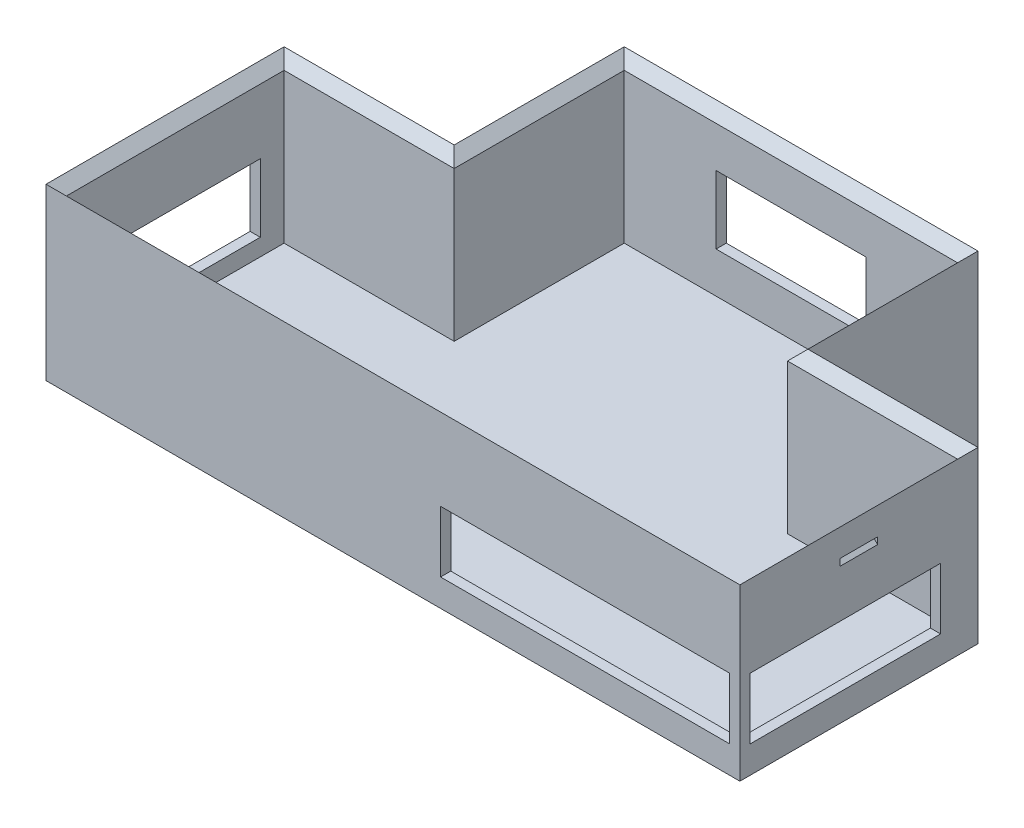
SolidWorks part; units mm, degrees
ref_plane "Front Plane" through (0, 0, 0) normal (0, 0, 1) x (1, 0, 0)
ref_plane "Top Plane" through (0, 0, 0) normal (0, 1, 0) x (1, 0, 0)
ref_plane "Right Plane" through (0, 0, 0) normal (1, 0, 0) x (0, 0, -1)
sketch "Sketch1" plane through (0, 0, 0) normal (0, 1, 0) x (1, 0, 0)
  line L12 (-88.7649, 6.3436) -> (115.2351, 6.3436)
  line L13 (115.2351, 6.3436) -> (115.2351, 76.3436)
  line L14 (115.2351, 76.3436) -> (65.2351, 76.3436)
  line L15 (65.2351, 76.3436) -> (65.2351, 126.3436)
  line L16 (65.2351, 126.3436) -> (-38.7649, 126.3436)
  line L17 (-38.7649, 126.3436) -> (-38.7649, 76.3436)
  line L18 (-38.7649, 76.3436) -> (-88.7649, 76.3436)
  line L19 (-88.7649, 76.3436) -> (-88.7649, 6.3436)
  dimension "D1" = 104
  dimension "D2" = 50
  dimension "D3" = 50
  dimension "D4" = 50
  dimension "D5" = 50
  dimension "D6" = 70
extrude "Boss-Extrude1" add sketch "Sketch1" along normal blind 50
sketch "Sketch4" plane through (0, 50, 0) normal (0, 1, 0) x (1, 0, 0)
  line L0 (-35.7649, 123.3436) -> (-35.7649, 73.3436)
  line L1 (-35.7649, 73.3436) -> (-85.7649, 73.3436)
  line L2 (-85.7649, 73.3436) -> (-85.7649, 9.3436)
  line L3 (-85.7649, 9.3436) -> (112.2351, 9.3436)
  line L4 (112.2351, 9.3436) -> (112.2351, 73.3436)
  line L5 (112.2351, 73.3436) -> (62.2351, 73.3436)
  line L6 (62.2351, 73.3436) -> (62.2351, 123.3436)
  line L7 (62.2351, 123.3436) -> (-35.7649, 123.3436)
  line L8 (65.2351, 126.3436) -> (-38.7649, 126.3436) construction
  line L9 (65.2351, 76.3436) -> (65.2351, 126.3436) construction
  line L10 (115.2351, 76.3436) -> (65.2351, 76.3436) construction
  line L11 (115.2351, 6.3436) -> (115.2351, 76.3436) construction
  line L12 (-88.7649, 6.3436) -> (115.2351, 6.3436) construction
  line L13 (-88.7649, 76.3436) -> (-88.7649, 6.3436) construction
  line L14 (-38.7649, 76.3436) -> (-88.7649, 76.3436) construction
  line L15 (-38.7649, 126.3436) -> (-38.7649, 76.3436) construction
  dimension "D1" = 3
  dimension "D2" = 3
  dimension "D3" = 3
  dimension "D4" = 3
  dimension "D5" = 3
  dimension "D6" = 3
  dimension "D7" = 3
  dimension "D8" = 3
extrude "Cut-Extrude1" cut sketch "Sketch4" against normal blind 47
chamfer "Chamfer3" distance 3 angle 45 8 edges at (13.2351, 50, -123.3436) (-35.7649, 50, -98.3436) (-60.7649, 50, -73.3436) (-85.7649, 50, -41.3436) (13.2351, 50, -9.3436) (112.2351, 50, -41.3436) (87.2351, 50, -73.3436) (62.2351, 50, -98.3436)
sketch "Sketch5" plane through (115.2351, 0, 0) normal (1, 0, 0) x (0, 0, -1)
  line L0 (6.3436, 50) -> (6.3436, 0) construction
  line L1 (9.3436, 26) -> (65.3436, 26)
  line L2 (9.3436, 26) -> (9.3436, 8)
  line L3 (9.3436, 8) -> (65.3436, 8)
  line L4 (65.3436, 26) -> (65.3436, 8)
  line L5 (6.3436, 0) -> (76.3436, 0) construction
  dimension "D1" = 3
  dimension "D2" = 8
  dimension "D3" = 56
  dimension "D4" = 18
extrude "Cut-Extrude2" cut sketch "Sketch5" against normal blind 3
sketch "Sketch6" plane through (0, 0, -6.3436) normal (0, 0, 1) x (1, 0, 0)
  line L0 (115.2351, 50) -> (115.2351, 0) construction
  line L1 (112.2351, 26) -> (27.2351, 26)
  line L2 (112.2351, 26) -> (112.2351, 8)
  line L3 (112.2351, 8) -> (27.2351, 8)
  line L4 (27.2351, 26) -> (27.2351, 8)
  line L5 (-88.7649, 0) -> (115.2351, 0) construction
  dimension "D1" = 3
  dimension "D2" = 8
  dimension "D3" = 18
  dimension "D4" = 85
extrude "Cut-Extrude3" cut sketch "Sketch6" against normal blind 3
sketch "Sketch7" plane through (-88.7649, 0, 0) normal (-1, 0, 0) x (0, 0, 1)
  line L0 (-76.3436, 0) -> (-6.3436, 0) construction
  line L1 (-66.3436, 28) -> (-16.3436, 28)
  line L2 (-66.3436, 28) -> (-66.3436, 8)
  line L3 (-66.3436, 8) -> (-16.3436, 8)
  line L4 (-16.3436, 28) -> (-16.3436, 8)
  line L5 (-6.3436, 50) -> (-6.3436, 0) construction
  line L6 (-76.3436, 50) -> (-76.3436, 0) construction
  dimension "D1" = 8
  dimension "D2" = 10
  dimension "D3" = 10
  dimension "D4" = 20
extrude "Cut-Extrude4" cut sketch "Sketch7" against normal blind 3
sketch "Sketch8" plane through (0, 0, -126.3436) normal (0, 0, -1) x (-1, 0, 0)
  line L0 (-65.2351, 0) -> (38.7649, 0) construction
  line L1 (-35.2351, 35) -> (8.7649, 35)
  line L2 (-35.2351, 35) -> (-35.2351, 15)
  line L3 (-35.2351, 15) -> (8.7649, 15)
  line L4 (8.7649, 35) -> (8.7649, 15)
  line L5 (-65.2351, 50) -> (-65.2351, 0) construction
  line L6 (38.7649, 50) -> (38.7649, 0) construction
  line L7 (-65.2351, 50) -> (38.7649, 50) construction
  point P12 (-13.2351, 50)
  dimension "D1" = 15
  dimension "D2" = 30
  dimension "D3" = 30
  dimension "D4" = 15
extrude "Cut-Extrude5" cut sketch "Sketch8" against normal blind 3
sketch "Sketch9" plane through (115.2351, 0, 0) normal (1, 0, 0) x (0, 0, -1)
  line L0 (6.3436, 50) -> (76.3436, 50) construction
  line L1 (35.8436, 42) -> (46.8436, 42)
  line L2 (35.8436, 42) -> (35.8436, 40)
  line L3 (35.8436, 40) -> (46.8436, 40)
  line L4 (46.8436, 42) -> (46.8436, 40)
  line L5 (76.3436, 50) -> (76.3436, 0) construction
  line L6 (6.3436, 50) -> (6.3436, 0) construction
  dimension "D1" = 8
  dimension "D2" = 29.5
  dimension "D3" = 29.5
  dimension "D4" = 2
extrude "Cut-Extrude6" cut sketch "Sketch9" against normal blind 1
draft "Draft3" type of draft neutral plane draft angle 45 faces to draft 2 face at (114.7351, 42, -41.3436) face at (114.7351, 40, -41.3436) neutral plane through (115.2351, 50, -6.3436) neutral plane normal (1, 0, 0) parameters "D1"=45
sketch "Sketch12" plane through (-88.7649, 0, 0) normal (-1, 0, 0) x (0, 0, 1)
  line L0 (-76.3436, 50) -> (-76.3436, 0) construction
  line L1 (-46.8436, 42) -> (-35.8436, 42)
  line L2 (-46.8436, 42) -> (-46.8436, 40)
  line L3 (-46.8436, 40) -> (-35.8436, 40)
  line L4 (-35.8436, 42) -> (-35.8436, 40)
  line L5 (-6.3436, 50) -> (-6.3436, 0) construction
  line L6 (-76.3436, 50) -> (-6.3436, 50) construction
  dimension "D1" = 29.5
  dimension "D2" = 29.5
  dimension "D3" = 8
  dimension "D4" = 2
extrude "Cut-Extrude7" cut sketch "Sketch12" against normal blind 1
draft "Draft4" type of draft neutral plane draft angle 45 faces to draft 2 face at (-88.2649, 42, -41.3436) face at (-88.2649, 40, -41.3436) neutral plane through (-88.7649, 50, -76.3436) neutral plane normal (-1, 0, 0) parameters "D1"=45
